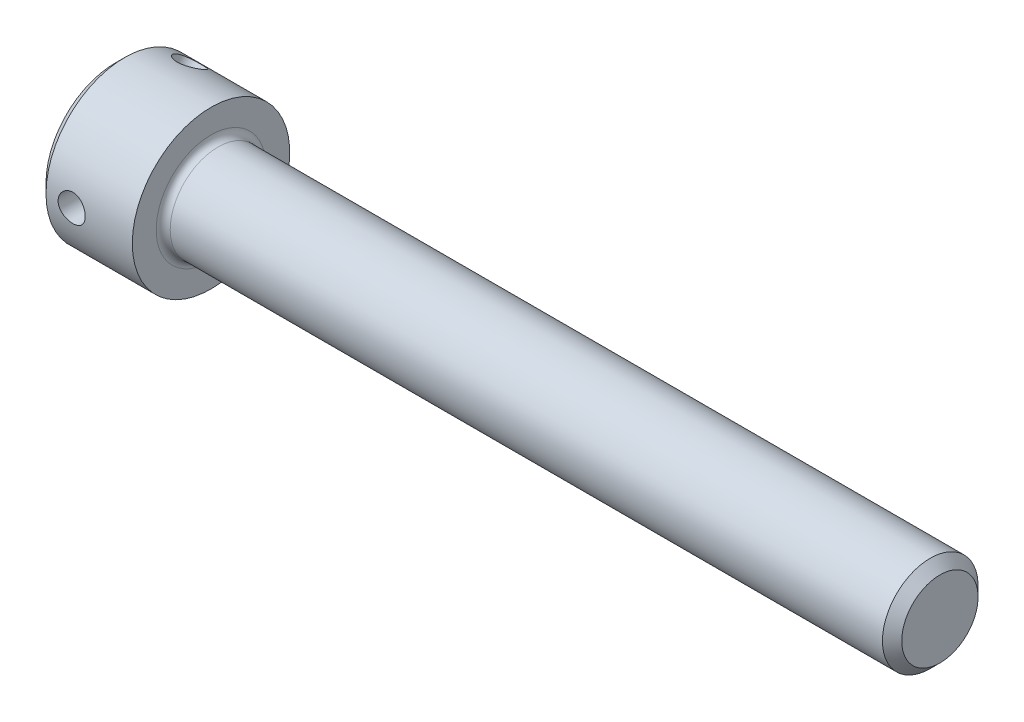
SolidWorks part; units mm, degrees
revolve "Base-Revolve" add sketch "BodySke"
sketch "BodySke" plane through (0, 0, 0) normal (0, 0, 1) x (1, 0, 0)
  line L0 (0, 0) -> (0, 3.0226)
  line L1 (0.4064, 3.429) -> (4.1656, 3.429)
  line L2 (4.1656, 3.429) -> (4.1656, 2.0828)
  line L3 (4.1656, 2.0828) -> (35.4952, 2.0828)
  line L4 (35.9156, 1.6624) -> (35.9156, 0)
  line L5 (35.9156, 0) -> (0, 0)
  line L6 (-31.75, 0) -> (127, 0) construction
  line L7 (0, 3.0226) -> (0.4064, 3.429)
  line L8 (35.9156, 1.6624) -> (35.4952, 2.0828)
  line L9 (0, -3.0226) -> (0.4064, -3.429) construction
  line L10 (35.9156, -1.6624) -> (35.4952, -2.0828) construction
  line L11 (4.8717, 9.525) -> (4.8717, 3.175) construction
  line L12 (13.6906, 9.525) -> (13.6906, 3.175) construction
  line L13 (-2.1844, 9.525) -> (-2.1844, 3.175) construction
  dimension "Diameter" = 4.1656
  dimension "Head_ht" = 4.1656
  dimension "Length" = 31.75
  dimension "Body_ch_ang" = 45
  dimension "Head_dia" = 6.858
  dimension "Head_ch_ang" = 45
  dimension "Head_side_ht" = 3.7592
  dimension "Minor_dia" = 3.3249
  dimension "Advance" = 0.7061
  dimension "Thread_nom" = 22.225
  dimension "Thread_length" = 38.1
cosmetic thread "ThreadCosmetic" [suppressed]
fillet "Fillet1" radius 0.3048 1 edges at (4.1656, 0, 2.0828)
ref_plane "Plane1" through (0, 0, 0) normal (0, 0, 1) x (1, 0, 0)
ref_plane "Plane2" through (0, 0, 0) normal (0, 1, 0) x (1, 0, 0)
ref_plane "Plane3" through (0, 0, 0) normal (1, 0, 0) x (0, 0, -1)
sketch "Sketch2" plane through (0, 0, 0) normal (0, 0, 1) x (1, 0, 0)
  line L0 (0, 1.778) -> (1.9558, 1.778)
  line L1 (1.9558, 1.778) -> (2.9823, 0)
  line L2 (-31.75, 0) -> (127, 0) construction
  line L3 (2.9823, 0) -> (0, 0)
  line L4 (0, 0) -> (0, 1.778)
  line L5 (0, 3.0226) -> (0, -3.0226) construction
  line L6 (0, 0) -> (47.625, 0) construction
  line L7 (4.1656, -3.429) -> (4.1656, 3.429) construction
  dimension "D1" = 1.778
  dimension "D2" = 60
revolve "Hex-PreBroach" cut sketch "Sketch2" angle 360 about L6
sketch "Sketch3" plane through (0, 0, 0) normal (-1, 0, 0) x (0, 0.5, 0.866)
  line L0 (1.0265, 1.778) -> (-1.0265, 1.778)
  line L1 (-1.0265, 1.778) -> (-2.0531, 0)
  line L2 (1.0265, 1.778) -> (2.0531, 0)
  line L3 (1.0265, -1.778) -> (2.0531, 0)
  line L4 (1.0265, -1.778) -> (-1.0265, -1.778)
  line L5 (-1.0265, -1.778) -> (-2.0531, 0)
  dimension "D1" = 1.778
  dimension "D2" = 1.778
extrude "Hex" cut sketch "Sketch3" against normal blind 1.9558
sketch "Sketch4" plane through (0, 0, 0) normal (-1, 0, 0) x (0, 0, 1)
  line L0 (0, 0) -> (2.1971, 0)
  line L1 (0, 0) -> (6.1484, 3.5498) construction
  line L2 (0, 0) -> (1.0985, 1.9027)
  line L3 (1.8302, 0.5287) -> (2.0897, 0.6786)
  line L4 (1.373, 1.3206) -> (1.6325, 1.4704)
  arc A0 (1.8302, 0.5287) -> (1.373, 1.3206) centre (0, 0) ccw
  arc A1 (2.1971, 0) -> (2.0897, 0.6786) centre (0, 0) ccw
  arc A2 (1.0985, 1.9027) -> (1.6325, 1.4704) centre (0, 0) cw
  dimension "D1" = 30
  dimension "D2" = 60
  dimension "Spline_p_dim" = 0.9144
  dimension "D3" = 0.4572
extrude "Spline" [suppressed] cut sketch "Sketch4" against normal blind 1.9558
pattern_circular "CirPattern1" [suppressed] count 6 every 60
sketch "Sketch5" plane through (0, 0, 0) normal (0, 0, 1) x (1, 0, 0)
  line L0 (-31.75, 0) -> (127, 0) construction
  line L2 (0, 3.0226) -> (0, -3.0226) construction
  circle A0 centre (1.524, 0) radius 0.5905
  dimension "Drilled_hole_dia" = 1.1811
  dimension "Drilled_hole_loc" = 1.524
extrude "Hole" cut sketch "Sketch5" against normal through all and the other way through all
pattern_circular "Drilled-4" count 2 every 60 about axis through (0, 0, 0) along (1, 0, 0) of "Hole"
pattern_circular "Drilled-6" [suppressed] count 3 every 60
sketch "ThdSchSke" plane through (0, 0, 0) normal (0, 0, 1) x (1, 0, 0)
  line L0 (13.6906, -1.6624) -> (13.3963, -2.0828)
  line L1 (13.6906, -1.6624) -> (13.9849, -2.0828)
  line L2 (13.9849, -2.0828) -> (13.9849, -2.6035)
  line L3 (-3.175, 0) -> (5.1513, 0) construction
  line L5 (13.9849, -2.6035) -> (13.3963, -2.6035)
  line L6 (13.3963, -2.6035) -> (13.3963, -2.0828)
  line L7 (0, 3.0226) -> (0, -3.0226) construction
  dimension "Thread_minor" = 3.3249
  dimension "Diameter" = 4.1656
revolve "ThreadSchematic" [suppressed] cut sketch "ThdSchSke" angle 360 about L3
pattern_linear "ThdSchPat" [suppressed]
equation "\"D2@Sketch3\" = \"Hex_size@Sketch3\" / 2"
equation "\"D1@Sketch3\" = \"Hex_size@Sketch3\" / 2"
equation "\"D1@Sketch2\" = \"Hex_size@Sketch3\" / 2"
equation "\"D3@Sketch4\" = \"Spline_p_dim@Sketch4\" / 2"
equation "\"Thread_minor@ThreadCosmetic\"  =  \"Minor_dia@BodySke\""
equation "\"D2@CirPattern1\" = 360 / \"Num_teeth@CirPattern1\""
equation "\"Wall_thickness@Sketch2\" = \"Head_ht@BodySke\" - \"Key_eng@Hex\""
equation "\"Thread_length@ThreadCosmetic\" = ((sgn( (\"Length@BodySke\" - \"Advance@BodySke\" ) - \"Thread_nom@BodySke\" )-1)*( (\"Length@BodySke\" - \"Advance@BodySke\" ) - \"Thread_nom@BodySke\" ))/-2+ \"Thread_nom@BodySke\""
equation "\"Thread_minor@ThdSchSke\" = \"Minor_dia@BodySke\""
equation "\"Diameter@ThdSchSke\" = \"Diameter@BodySke\""
equation "\"Overcut@ThdSchSke\" = \"Diameter@BodySke\" * 1.25"
equation "\"Start@ThdSchSke\" = \"Head_ht@BodySke\" + \"Length@BodySke\" - \"Thread_length@ThreadCosmetic\"  '---Non-countersunk---"
equation "\"Num_threads@ThdSchPat\" = int( \"Thread_length@ThreadCosmetic\" / \"Advance@BodySke\" + 0.999 )  + 1"
equation "\"Advance@ThdSchPat\" = \"Thread_length@ThreadCosmetic\" /  (\"Num_threads@ThdSchPat\" - 1) 'relax it"
equation "\"Num_threads@ThdSchPat\" = \"Num_threads@ThdSchPat\" - sgn( \"Num_threads@ThdSchPat\" - 1) '---chamfered tips only---"
